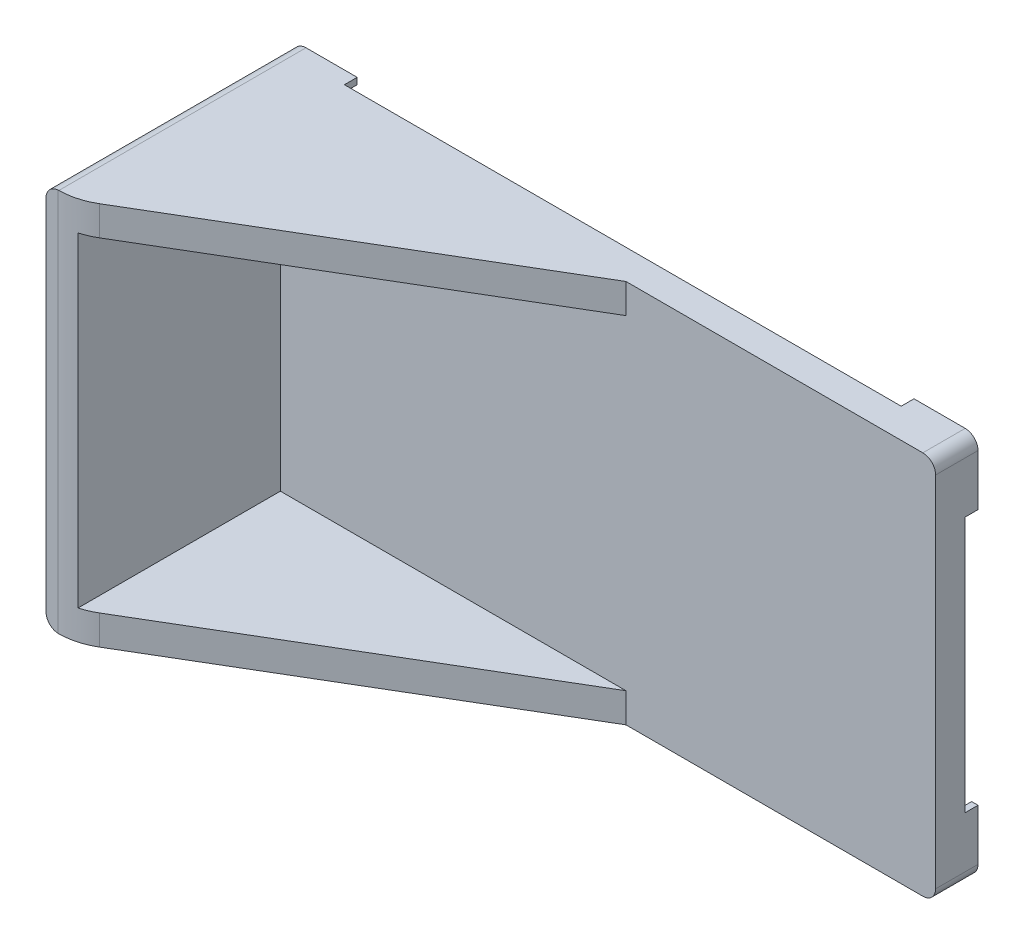
SolidWorks part; units mm, degrees
ref_plane "Front Plane" through (0, 0, 0) normal (0, 0, 1) x (1, 0, 0)
ref_plane "Top Plane" through (0, 0, 0) normal (0, 1, 0) x (1, 0, 0)
ref_plane "Right Plane" through (0, 0, 0) normal (1, 0, 0) x (0, 0, -1)
sketch "Sketch1" plane through (0, 0, 0) normal (0, 0, 1) x (1, 0, 0)
  line L0 (0, 0) -> (69.5837, 0) construction
  line L1 (-26.75, -15) -> (26.75, -15)
  line L2 (-26.75, -15) -> (-26.75, 15)
  line L3 (-26.75, 15) -> (26.75, 15)
  line L4 (26.75, -15) -> (26.75, 15)
  line L5 (0, 0) -> (0, 25.4154) construction
  dimension "D1" = 30
  dimension "D2" = 53.5
extrude "Boss-Extrude1" add sketch "Sketch1" along normal blind 2.3114
sketch "Sketch2" plane through (0, 0, 2.3114) normal (0, 0, 1) x (1, 0, 0)
  line L0 (-26.75, -15) -> (26.75, -15) construction
  line L1 (-26.75, 15) -> (-24.4386, 15)
  line L2 (-26.75, 15) -> (-26.75, -15)
  line L3 (-26.75, -15) -> (-24.4386, -15)
  line L4 (-24.4386, 15) -> (-24.4386, -15)
  dimension "D1" = 2.3114
extrude "Boss-Extrude2" add sketch "Sketch2" along normal blind 16
sketch "Sketch3" plane through (0, -15, 0) normal (0, -1, 0) x (1, 0, 0)
  line L0 (-24.4386, 18.3114) -> (2.5614, 2.3114)
  line L1 (-24.4386, 2.3114) -> (26.75, 2.3114) construction
  line L2 (-24.4386, 18.3114) -> (-24.4386, 2.3114) construction
  line L3 (-24.4386, 18.3114) -> (-24.4386, 2.3114)
  line L4 (-24.4386, 2.3114) -> (2.5614, 2.3114)
  line L5 (-26.75, 18.3114) -> (-24.4386, 18.3114) construction
  dimension "D1" = 27
extrude "Boss-Extrude3" add sketch "Sketch3" against normal blind 2.3114
mirror "Mirror1" about plane through (0, 0, 0) normal (0, 1, 0) of "Boss-Extrude3"
fillet "Fillet1" radius 1 4 edges at (26.75, 15, 1.1557) (26.75, -15, 1.1557) (-26.75, 15, 9.1557) (-26.75, -15, 9.1557)
fillet "Fillet2" radius 5 1 edges at (-24.4386, 13.8443, 18.3114) tangent propagation no
sketch "Sketch7" plane through (0, 0, 0) normal (0, 0, -1) x (-1, 0, 0)
  line L0 (-25.75, 15) -> (-21.75, 15)
  line L1 (-25.75, 15) -> (25.75, 15) construction
  line L2 (-26.75, 14) -> (-26.75, 10)
  line L3 (-26.75, -14) -> (-26.75, 14) construction
  line L4 (-25.75, 14.5) -> (-21.75, 14.5)
  line L5 (-26.25, 14) -> (-26.25, 10)
  line L6 (-26.25, 10) -> (-26.75, 10)
  line L7 (-21.75, 14.5) -> (-21.75, 15)
  arc A0 (-25.75, 15) -> (-26.75, 14) centre (-25.75, 14) ccw construction
  arc A4 (-25.75, 15) -> (-26.75, 14) centre (-25.75, 14) ccw
  arc A8 (-25.75, 14.5) -> (-26.25, 14) centre (-25.75, 14) ccw
  dimension "D1" = 5
  dimension "D2" = 0.5
extrude "Boss-Extrude5" add sketch "Sketch7" along normal blind 1
mirror "Mirror2" about plane through (0, 0, 0) normal (0, 1, 0) of "Boss-Extrude5"
mirror "Mirror3" about plane through (0, 0, 0) normal (1, 0, 0) of "Mirror2", "Boss-Extrude5"
